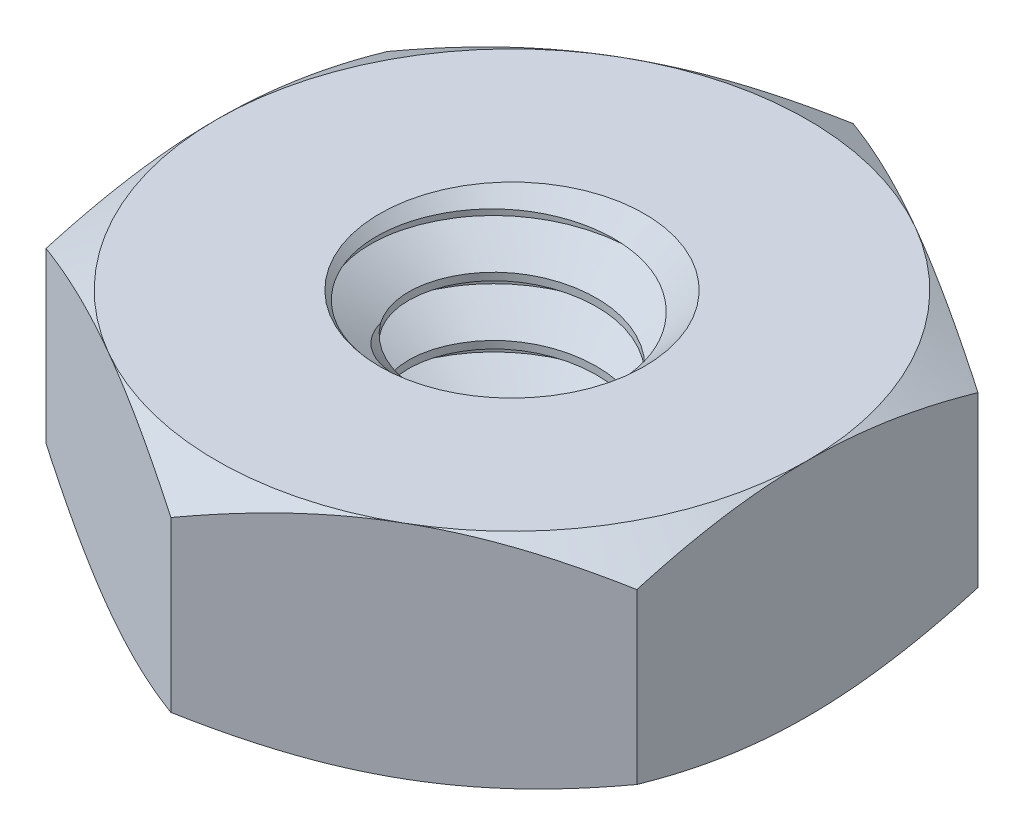
SolidWorks part; units mm, degrees
ref_plane "Front Plane" through (0, 0, 0) normal (0, 0, 1) x (1, 0, 0)
ref_plane "Top Plane" through (0, 0, 0) normal (0, 1, 0) x (1, 0, 0)
ref_plane "Right Plane" through (0, 0, 0) normal (1, 0, 0) x (0, 0, -1)
sketch "Sketch7" plane through (0, 0, 0) normal (0, 1, 0) x (1, 0, 0)
  line L0 (-3.175, 0) -> (3.175, 0) construction
  line L1 (-1.4224, 0) -> (1.4224, 0) construction
  line L2 (-3.175, 0) -> (-3.175, -0.635) construction
  point P4 (0, 0)
  point P8 (0, 0)
sketch "Sketch6" plane through (0, 0, 0) normal (1, 0, 0) x (0, 0, -1)
  line L0 (0, 1.1906) -> (0, -1.1906) construction
  point P4 (0, 0)
sketch "Sketch1" plane through (0, 0, 0) normal (0, 1, 0) x (1, 0, 0)
  line L1 (-3.175, 1.8331) -> (-3.175, -1.8331)
  line L2 (-3.175, -1.8331) -> (0, -3.6662)
  line L3 (0, -3.6662) -> (3.175, -1.8331)
  line L4 (3.175, -1.8331) -> (3.175, 1.8331)
  line L5 (3.175, 1.8331) -> (0, 3.6662)
  line L6 (0, 3.6662) -> (-3.175, 1.8331)
  circle A0 centre (0, 0) radius 3.175 construction
  circle A1 centre (0, 0) radius 1.4224
extrude "Boss-Extrude1" add sketch "Sketch1" along normal mid plane 2.3813
sketch "Sketch5" plane through (0, 1.1906, 0) normal (0, 1, 0) x (1, 0, 0)
  circle A0 centre (0, 0) radius 3.175 construction
  circle A1 centre (0, 0) radius 3.175
extrude "Cut-Extrude2" cut sketch "Sketch5" against normal through all draft 60 flip side to cut
mirror "Mirror1" about plane through (0, 0, 0) normal (0, 1, 0) of "Cut-Extrude2"
sketch "Sketch14" plane through (0, 1.1906, 0) normal (0, 1, 0) x (1, 0, 0)
  line L0 (-1.4224, 0) -> (1.4224, 0) construction
  line L1 (0, 1.4224) -> (0, -1.4224) construction
  circle A0 centre (0, 0) radius 1.4224 construction
  point P7 (0, 0)
  point P11 (0, 0)
  point P12 (0, -1.4224)
  point P13 (-1.4224, 0)
  point P14 (0, 1.4224)
  point P15 (1.4224, 0)
sketch "Sketch8" plane through (0, 1.1906, 0) normal (0, 1, 0) x (1, 0, 0)
  circle A0 centre (0, 0) radius 1.4224 construction
  circle A1 centre (0, 0) radius 1.4224
extrude "Boss-Extrude2" add sketch "Sketch8" against normal up to surface (2.3813 mm away) separate body up to face at (0, -1.1906, 0)
sketch "Sketch9" plane through (0, 1.1906, 0) normal (0, 1, 0) x (1, 0, 0)
  circle A0 centre (0, 0) radius 1.4224 construction
  circle A1 centre (0, 0) radius 1.4224
extrude "Boss-Extrude3" add sketch "Sketch9" against normal up to surface (2.3813 mm away) up to face at (0, -1.1906, 0)
sketch "Sketch10" plane through (0, 1.1906, 0) normal (0, 1, 0) x (1, 0, 0)
  circle A0 centre (0, 0) radius 1.4224 construction
  circle A1 centre (0, 0) radius 1.4224
curve "Helix/Spiral1" pitch 0.635 height 3.0162 radius 1.4224 centre (0, 1.1906, 0) axis (0, -1, 0) start towards (0, 0, 1)
sketch "Sketch11" plane through (0, 0, 0) normal (1, 0, 0) x (0, 0, -1)
  line L0 (-1.4224, 1.1906) -> (-1.4224, 1.7462)
  line L1 (1.4224, 1.1906) -> (-1.4224, 1.1906) construction
  line L2 (-1.4224, 1.7462) -> (-1.01, 1.5081)
  line L3 (-1.01, 1.5081) -> (-1.01, 1.4287)
  line L4 (-1.01, 1.4287) -> (-1.4224, 1.1906)
  line L5 (-1.4224, 1.4684) -> (-1.01, 1.4684) construction
  line L6 (-1.2162, 1.6272) -> (-1.2162, 1.3097) construction
  spline S0 degree 3 poles (-1.4224, 1.1906) (-1.4224, 1.1773) (-1.3463, 1.1504) (-1.0218, 1.1102) (-0.5376, 1.07) (0.0306, 1.0298) (0.594, 0.9895) (1.0646, 0.9493) (1.3688, 0.9091) (1.4592, 0.8689) (1.3214, 0.8287) (0.9772, 0.7885) (0.4803, 0.7482) (-0.0917, 0.708) (-0.6494, 0.6678) (-1.1055, 0.6276) (-1.389, 0.5874) (-1.4553, 0.5472) (-1.2942, 0.5069) (-0.9309, 0.4667) (-0.4221, 0.4265) (0.1527, 0.3863) (0.7036, 0.3461) (1.1445, 0.3059) (1.4066, 0.2656) (1.4489, 0.2254) (1.2648, 0.1852) (0.883, 0.145) (0.3632, 0.1048) (-0.2133, 0.0646) (-0.7565, 0.0243) (-1.1815, -0.0159) (-1.4219, -0.0561) (-1.44, -0.0963) (-1.2331, -0.1365) (-0.8335, -0.1767) (-0.3036, -0.217) (0.2737, -0.2572) (0.8082, -0.2974) (1.2164, -0.3376) (1.4346, -0.3778) (1.4285, -0.418) (1.1992, -0.4583) (0.7825, -0.4985) (0.2436, -0.5387) (-0.3335, -0.5789) (-0.8584, -0.6191) (-1.2492, -0.6593) (-1.4448, -0.6996) (-1.4146, -0.7398) (-1.1633, -0.78) (-0.7302, -0.8202) (-0.183, -0.8604) (0.3927, -0.9006) (0.9071, -0.9409) (1.2798, -0.9811) (1.4524, -1.0213) (1.3981, -1.0615) (1.1253, -1.1017) (0.6766, -1.1419) (0.1222, -1.1822) (-0.4513, -1.2224) (-0.9543, -1.2626) (-1.3081, -1.3028) (-1.4576, -1.343) (-1.3792, -1.3832) (-1.0853, -1.4235) (-0.6218, -1.4637) (-0.0612, -1.5039) (0.5091, -1.5441) (0.9997, -1.5843) (1.3342, -1.6245) (1.4601, -1.6648) (1.3579, -1.705) (1.0433, -1.7452) (0.5665, -1.7854) (0.1874, -1.8123) (0, -1.8256) knots 0 0 0 0 0.013333 0.026667 0.04 0.053333 0.066667 0.08 0.093333 0.106667 0.12 0.133333 0.146667 0.16 0.173333 0.186667 0.2 0.213333 0.226667 0.24 0.253333 0.266667 0.28 0.293333 0.306667 0.32 0.333333 0.346667 0.36 0.373333 0.386667 0.4 0.413333 0.426667 0.44 0.453333 0.466667 0.48 0.493333 0.506667 0.52 0.533333 0.546667 0.56 0.573333 0.586667 0.6 0.613333 0.626667 0.64 0.653333 0.666667 0.68 0.693333 0.706667 0.72 0.733333 0.746667 0.76 0.773333 0.786667 0.8 0.813333 0.826667 0.84 0.853333 0.866667 0.88 0.893333 0.906667 0.92 0.933333 0.946667 0.96 0.973333 0.986667 1 1 1 1 construction
  dimension "D1" = 60
  dimension "D2" = 0.0794
  dimension "D3" = 0.3175
sweep "Cut-Sweep1" cut profiles "Sketch11" path "Helix/Spiral1" align with end faces yes
combine bodies "Combine1" operation type subtract main body 107 bodies to subtract 108
sketch "Sketch12" plane through (0, 1.1906, 0) normal (0, 1, 0) x (1, 0, 0)
  circle A1 centre (0, 0) radius 1.4224
  circle A2 centre (0, 0) radius 1.4224
  dimension "D1" = 0
extrude "Cut-Extrude3" cut sketch "Sketch12" against normal through all draft 45
sketch "Sketch13" plane through (0, -1.1906, 0) normal (0, -1, 0) x (1, 0, 0)
  circle A1 centre (0, 0) radius 1.4224
  circle A2 centre (0, 0) radius 1.4224
  dimension "D1" = 0
extrude "Cut-Extrude4" cut sketch "Sketch13" against normal through all draft 45
equation "\"D3@Helix/Spiral1\"=\"Thickness@Sketch6\"+\"Pitch@Sketch7\""
equation "\"Height@Boss-Extrude1\"=\"Thickness@Sketch6\""
equation "\"D4@Helix/Spiral1\"=\"Pitch@Sketch7\""
equation "\"D2@Sketch11\"=\"Pitch@Sketch7\"*.125"
equation "\"D3@Sketch11\"=\"Pitch@Sketch7\"*.5"
